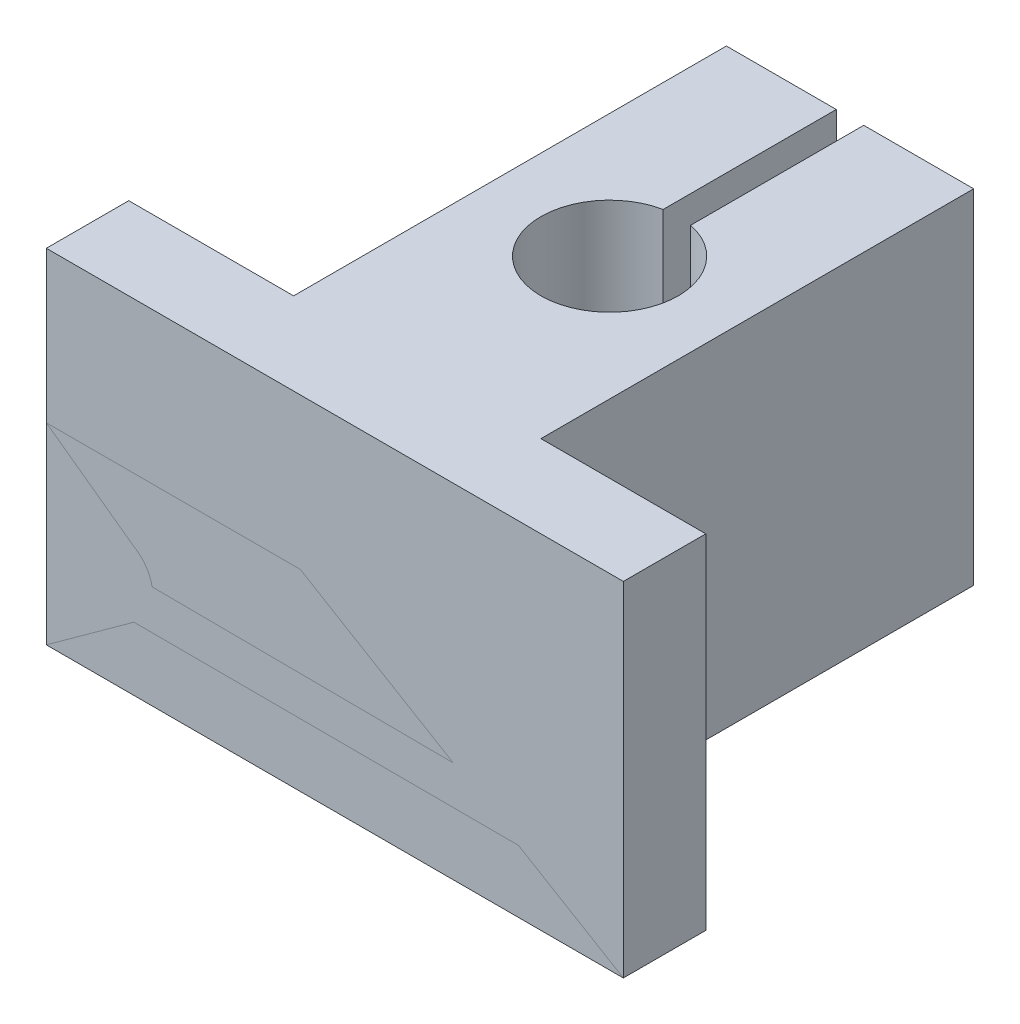
SolidWorks part; units mm, degrees
ref_plane "Спереди" through (0, 0, 0) normal (0, 0, 1) x (1, 0, 0)
ref_plane "Сверху" through (0, 0, 0) normal (0, 1, 0) x (1, 0, 0)
ref_plane "Справа" through (0, 0, 0) normal (1, 0, 0) x (0, 0, -1)
sketch "Эскиз2" plane through (0, 0, 0) normal (0, 1, 0) x (1, 0, 0)
  line L0 (-21, 0) -> (-9, 0)
  line L1 (-9, 31.5) -> (-9, 0)
  line L2 (-9, 31.5) -> (-1, 31.5)
  line L3 (9, 31.5) -> (9, 0)
  line L4 (9, 0) -> (21, 0)
  line L5 (21, 0) -> (21, -6)
  line L6 (21, -6) -> (-21, -6)
  line L7 (-21, -6) -> (-21, 0)
  line L8 (-1, 31.5) -> (-1, 18.899)
  line L9 (1, 31.5) -> (1, 18.899)
  line L10 (0, -6) -> (0, 31.5) construction
  line L11 (-9, 14) -> (9, 14) construction
  line L12 (-16, 0) -> (-16, -6) construction
  line L13 (16, 0) -> (16, -6) construction
  line L14 (1, 31.5) -> (9, 31.5)
  line L15 (-9, 26.5) -> (9, 26.5) construction
  arc A0 (-1, 18.899) -> (1, 18.899) centre (0, 14) ccw
  dimension "D3" = 10
  dimension "D1" = 20
  dimension "D2" = 6
  dimension "D4" = 37.5
  dimension "D5" = 18
  dimension "D6" = 32
  dimension "D7" = 42
  dimension "D8" = 2
  dimension "D9" = 5
extrude "Бобышка-Вытянуть2" add sketch "Эскиз2" along normal blind 25
extrude "Бобышка-Вытянуть6" add sketch "Эскиз2<2>" along normal blind 14 separate body
sketch "Эскиз2<2>" plane through (0, 0, 0) normal (0, 1, 0) x (1, 0, 0) same geometry as "Эскиз2"
sketch "Эскиз5" plane through (0, 0, 0) normal (0, 0, -1) x (-1, 0, 0)
  line L0 (-21, 7) -> (21, 7) construction
  line L1 (-21, 14) -> (-21, 0) construction
  line L2 (21, 14) -> (21, 0) construction
  line L3 (-16, 14) -> (-16, 0) construction
  line L4 (-21, 14) -> (-9, 14) construction
  line L5 (16, 14) -> (16, 0) construction
  line L6 (9, 14) -> (21, 14) construction
  line L7 (0, 14) -> (0, 0) construction
  line L8 (5, 14) -> (-5, 14) construction
  circle A0 centre (-16, 7) radius 2.75
  circle A1 centre (16, 7) radius 2.75
  point P19 (-11.8103, 7)
  point P24 (-16, 7.1496)
  point P25 (16, 7)
  dimension "D2" = 5.5
  dimension "D1" = 32
extrude "Вырез-Вытянуть1" cut sketch "Эскиз5" against normal through all
sketch "Эскиз6" plane through (-9, 0, 0) normal (-1, 0, 0) x (0, 0, 1)
  line L0 (-31.5, 7) -> (0, 7) construction
  line L1 (-31.5, 14) -> (-31.5, 0) construction
  line L2 (0, 14) -> (0, 0) construction
  circle A0 centre (-26.5, 7) radius 2
  point P6 (0, 7)
  point P9 (-24.4154, 7)
  dimension "D1" = 4
  dimension "D2" = 5
extrude "Вырез-Вытянуть2" cut sketch "Эскиз6" against normal through all
